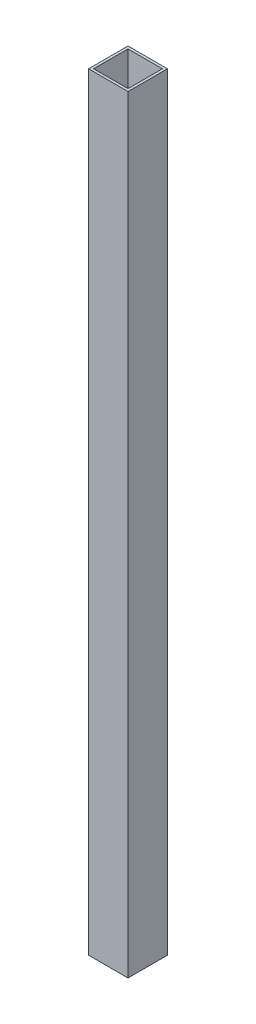
SolidWorks part; units mm, degrees
ref_plane "Front Plane" through (0, 0, 0) normal (0, 0, 1) x (1, 0, 0)
ref_plane "Top Plane" through (0, 0, 0) normal (0, 1, 0) x (1, 0, 0)
ref_plane "Right Plane" through (0, 0, 0) normal (1, 0, 0) x (0, 0, -1)
sketch "Sketch1" plane through (0, 0, 0) normal (0, 1, 0) x (1, 0, 0)
  line L1 (-9.5, -9.5) -> (9.5, -9.5)
  line L2 (-9.5, -9.5) -> (-9.5, 9.5)
  line L3 (-9.5, 9.5) -> (9.5, 9.5)
  line L4 (9.5, -9.5) -> (9.5, 9.5)
  line L5 (-9.5, -9.5) -> (9.5, 9.5) construction
  line L6 (-9.5, 9.5) -> (9.5, -9.5) construction
  line L7 (-8.3, -8.3) -> (8.3, -8.3)
  line L8 (-8.3, -8.3) -> (-8.3, 8.3)
  line L9 (-8.3, 8.3) -> (8.3, 8.3)
  line L10 (8.3, -8.3) -> (8.3, 8.3)
  line L11 (-8.3, -8.3) -> (8.3, 8.3) construction
  line L12 (-8.3, 8.3) -> (8.3, -8.3) construction
  point P0 (0, 0)
  point P6 (0, 0)
  dimension "D1" = 1.2
  dimension "D2" = 1.2
  dimension "D3" = 19
extrude "Boss-Extrude1" add sketch "Sketch1" along normal mid plane 370
